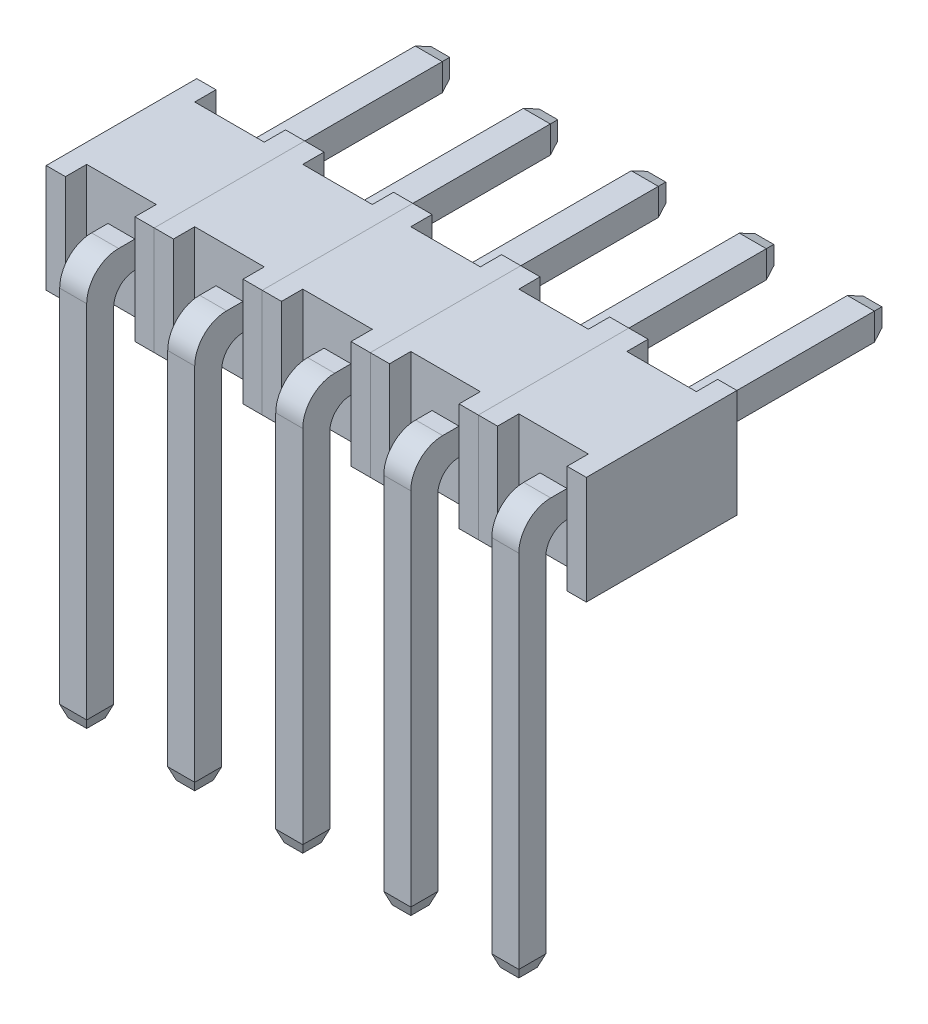
SolidWorks part; units mm, degrees
ref_plane "Front Plane" through (0, 0, 0) normal (0, 0, 1) x (1, 0, 0)
ref_plane "Top Plane" through (0, 0, 0) normal (0, 1, 0) x (1, 0, 0)
ref_plane "Right Plane" through (0, 0, 0) normal (1, 0, 0) x (0, 0, -1)
sketch "Sketch1" plane through (0, 0, 0) normal (0, 0, 1) x (1, 0, 0)
  line L0 (2.54, 10.4525) -> (2.54, 7.9125) construction
  line L1 (0, 10.4525) -> (13.2523, 10.4525)
  line L2 (0, 10.4525) -> (0, 7.9125)
  line L3 (0, 7.9125) -> (13.2523, 7.9125)
  line L4 (13.2523, 10.4525) -> (13.2523, 7.9125)
  line L5 (1.5875, 9.5) -> (0.9525, 9.5)
  line L6 (1.5875, 9.5) -> (1.5875, 0)
  line L7 (1.5875, 0) -> (0.9525, 0)
  line L8 (0.9525, 9.5) -> (0.9525, 0)
  line L9 (3.4925, 9.5) -> (4.1275, 9.5)
  line L10 (3.4925, 9.5) -> (3.4925, 0)
  line L11 (3.4925, 0) -> (4.1275, 0)
  line L12 (4.1275, 9.5) -> (4.1275, 0)
  line L14 (0.9525, 8.865) -> (1.5875, 8.865)
  line L15 (0.9525, 8.865) -> (0.9525, 9.5)
  line L16 (0.9525, 9.5) -> (1.5875, 9.5)
  line L17 (1.5875, 8.865) -> (1.5875, 9.5)
  line L18 (0.9525, 8.865) -> (1.5875, 9.5) construction
  line L19 (0.9525, 9.5) -> (1.5875, 8.865) construction
  point P12 (1.27, 9.5)
  point P16 (1.27, 9.1825)
  point P22 (0, 9.1825)
  dimension "D1" = 0.635
  dimension "D2" = 2.54
  dimension "D3" = 2.54
  dimension "D4" = 1.27
  dimension "D5" = 2.54
  dimension "D6" = 9.5
sketch "Sketch2" plane through (0, 0, 0) normal (0, 0, 1) x (1, 0, 0)
  line L1 (0.9525, 0) -> (1.5875, 0)
  line L2 (0.9525, 0) -> (0.9525, 9.5)
  line L3 (0.9525, 9.5) -> (1.5875, 9.5)
  line L4 (1.5875, 0) -> (1.5875, 9.5)
extrude "Boss-Extrude1" add sketch "Sketch2" against normal blind 0.635
sketch "Sketch3" plane through (0, 0, -0.635) normal (0, 0, -1) x (-1, 0, 0)
  line L0 (-1.5875, 0) -> (-1.5875, 9.5) construction
  line L1 (-0.9525, 9.5) -> (-1.5875, 9.5)
  line L2 (-0.9525, 9.5) -> (-0.9525, 8.865)
  line L3 (-0.9525, 8.865) -> (-1.5875, 8.865)
  line L4 (-1.5875, 9.5) -> (-1.5875, 8.865)
extrude "Boss-Extrude2" add sketch "Sketch3" along normal blind 8
fillet "Fillet1" radius 0.5 1 edges at (1.27, 8.865, -0.635)
fillet "Fillet2" radius 0.75 1 edges at (1.27, 9.5, 0)
sketch "Sketch4" plane through (0, 0, -0.635) normal (0, 0, -1) x (-1, 0, 0)
  line L0 (0, 7.9125) -> (-13.2523, 7.9125) construction
  line L1 (0, 10.4525) -> (-0.4525, 10.4525)
  line L2 (0, 10.4525) -> (0, 7.9125)
  line L3 (0, 7.9125) -> (-0.4525, 7.9125)
  line L4 (-0.4525, 10.4525) -> (-0.4525, 7.9125)
  line L5 (-0.9525, 9.5) -> (-0.9525, 0) construction
  line L6 (-2.54, 10.4525) -> (-2.0875, 10.4525)
  line L7 (-2.54, 10.4525) -> (-2.54, 7.9125)
  line L8 (-2.54, 7.9125) -> (-2.0875, 7.9125)
  line L9 (-2.0875, 10.4525) -> (-2.0875, 7.9125)
  dimension "D1" = 0.5
extrude "Boss-Extrude3" add sketch "Sketch4" along normal blind 0.5 separate body
sketch "Sketch5" plane through (0, 0, -1.135) normal (0, 0, -1) x (-1, 0, 0)
  line L1 (-2.54, 10.4525) -> (0, 10.4525)
  line L2 (-2.54, 10.4525) -> (-2.54, 7.9125)
  line L3 (-2.54, 7.9125) -> (0, 7.9125)
  line L4 (0, 10.4525) -> (0, 7.9125)
extrude "Boss-Extrude4" add sketch "Sketch5" along normal blind 2.54
sketch "Sketch6" plane through (0, 0, -3.675) normal (0, 0, -1) x (-1, 0, 0)
  line L1 (-0.4525, 10.4525) -> (0, 10.4525)
  line L2 (-0.4525, 10.4525) -> (-0.4525, 7.9125)
  line L3 (-0.4525, 7.9125) -> (0, 7.9125)
  line L4 (0, 10.4525) -> (0, 7.9125)
  line L5 (-2.0875, 10.4525) -> (-2.54, 10.4525)
  line L6 (-2.0875, 10.4525) -> (-2.0875, 7.9125)
  line L7 (-2.0875, 7.9125) -> (-2.54, 7.9125)
  line L8 (-2.54, 10.4525) -> (-2.54, 7.9125)
extrude "Boss-Extrude5" add sketch "Sketch6" along normal blind 0.5
chamfer "Chamfer1" distance 0.1 angle 70 4 edges at (1.27, 8.865, -8.635) (1.5875, 9.1825, -8.635) (1.27, 9.5, -8.635) (0.9525, 9.1825, -8.635) first distance on face at (1.27, 9.1825, -8.635)
chamfer "Chamfer2" distance 0.1 angle 70 4 edges at (1.5875, 0, -0.3175) (1.27, 0, -0.635) (0.9525, 0, -0.3175) (1.27, 0, 0) first distance on face at (1.27, 0, -0.3175)
pattern_linear "Num pins" count 5 spacing 2.54 along (1, 0, 0) of bodies 106
